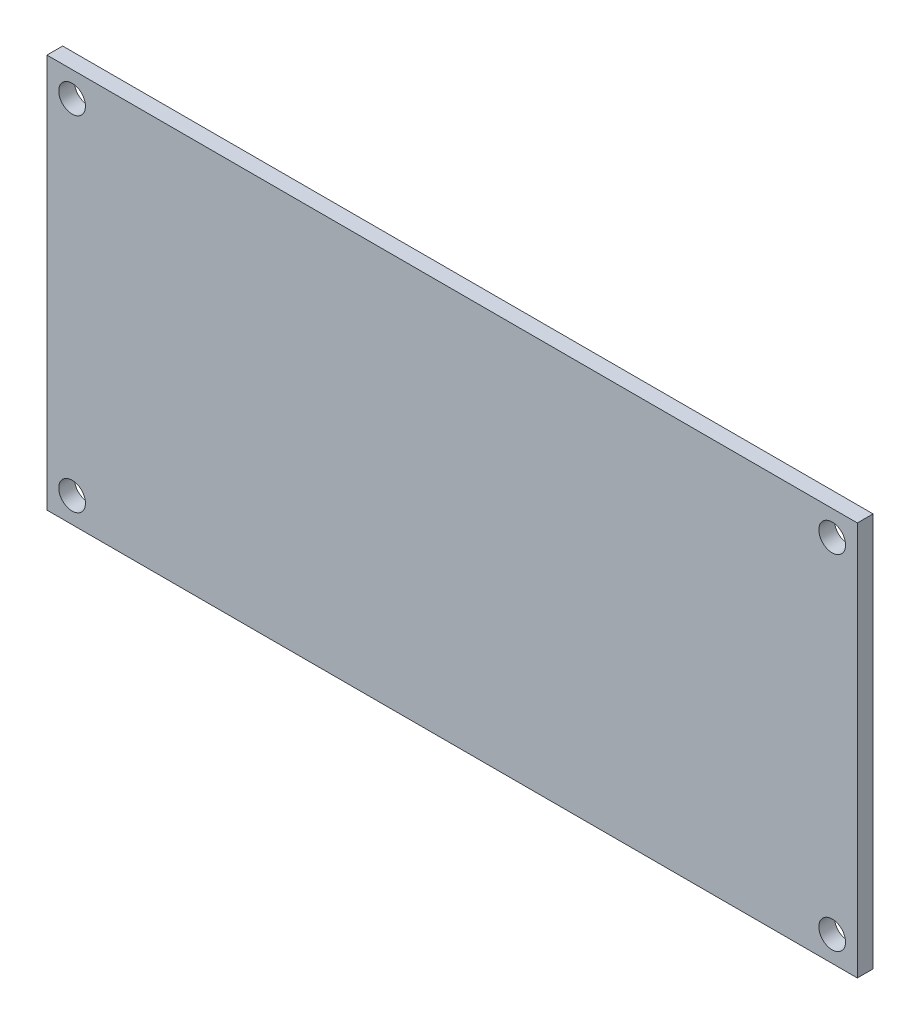
SolidWorks part; units mm, degrees
ref_plane "Front Plane" through (0, 0, 0) normal (0, 0, 1) x (1, 0, 0)
ref_plane "Top Plane" through (0, 0, 0) normal (0, 1, 0) x (1, 0, 0)
ref_plane "Right Plane" through (0, 0, 0) normal (1, 0, 0) x (0, 0, -1)
sketch "Sketch1" plane through (0, 0, 0) normal (0, 0, 1) x (1, 0, 0)
  line L0 (3106.2388, 1129.5477) -> (3106.2388, 1169.3637) construction
  line L1 (3118.5808, 1129.5477) -> (3142.0968, 1129.5477) construction
  line L3 (3094.4808, 1129.5477) -> (3117.9968, 1129.5477) construction
  line L4 (3117.9968, 1169.3637) -> (3094.4808, 1169.3637) construction
  line L6 (3065.3008, 1169.3637) -> (3147.1768, 1169.3637)
  line L7 (3065.3008, 1169.3637) -> (3065.3008, 1129.5477)
  line L8 (3065.3008, 1129.5477) -> (3147.1768, 1129.5477)
  line L9 (3147.1768, 1169.3637) -> (3147.1768, 1129.5477)
  line L10 (3065.3008, 1169.3637) -> (3147.1768, 1129.5477) construction
  line L11 (3065.3008, 1129.5477) -> (3147.1768, 1169.3637) construction
  point P6 (3106.2388, 1149.4557)
  dimension "D1" = 2.54
extrude "Boss-Extrude1" add sketch "Sketch1" along normal blind 1.5875
hole_wizard "Ø2.7 (2.7) Diameter Hole1" positions "Sketch3" profile "Sketch2" hole size "Ø2.7" standard "ANSI Metric" end condition through all
sketch "Sketch3" plane through (0, 0, 1.5875) normal (0, 0, 1) x (1, 0, 0)
  line L0 (3147.1768, 1129.5477) -> (3147.1768, 1169.3637) construction
  line L1 (3065.3008, 1129.5477) -> (3147.1768, 1129.5477) construction
  line L2 (3106.2388, 1129.5477) -> (3106.2388, 1149.4557) construction
  line L3 (3106.2388, 1149.4557) -> (3065.3008, 1149.4557) construction
  line L4 (3065.3008, 1169.3637) -> (3065.3008, 1129.5477) construction
  point P0 (3144.6368, 1132.0877)
  point P14 (3067.8408, 1132.0877)
  point P16 (3144.6368, 1166.8237)
  point P17 (3067.8408, 1166.8237)
  dimension "D1" = 2.54
  dimension "D2" = 2.54
sketch "Sketch2" plane through (3144.6368, 1132.0877, 1.5875) normal (1, 0, 0) x (0, -1, 0)
  line L0 (0, 0) -> (0, 1.5875)
  line L1 (0, 1.5875) -> (1.35, 1.5875)
  line L2 (1.35, 1.5875) -> (1.35, 0)
  line L5 (1.35, 0) -> (0, 0)
  line L11 (0, -6.35) -> (0, 107.95) construction
  dimension "Thru Hole Dia." = 2.7
  dimension "Thru Hole Depth" = 1.5875
